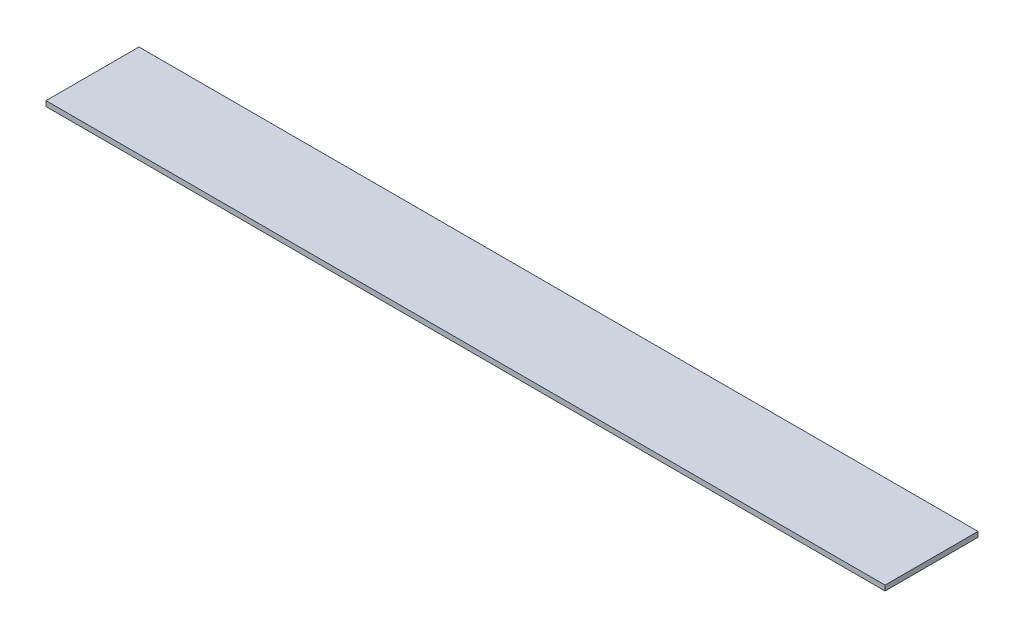
SolidWorks part; units mm, degrees
material "Liga 7079"
ref_plane "Plano frontal" through (0, 0, 0) normal (0, 0, 1) x (1, 0, 0)
ref_plane "Plano superior" through (0, 0, 0) normal (0, 1, 0) x (1, 0, 0)
ref_plane "Plano direito" through (0, 0, 0) normal (1, 0, 0) x (0, 0, -1)
sketch "Esboço1" plane through (0, 0, 0) normal (1, 0, 0) x (0, 0, -1)
  line L1 (-18, 0) -> (18, 0)
  dimension "D1" = 36
sheet metal parameters "Chapa metálica2" thickness 2 parameters "D1"=0.7366, "Espessura"=2
base flange "Flange-base2" sketch "Esboço1" end condition mid plane depth 325 reverse direction no thickness 2 reverse thickness direction no bend radius 0.7366
flat pattern "Padrão-Plano2" [suppressed]
sketch "Curva-Linhas2" plane through (0, 0, 0) normal (0, 1, 0) x (-1, 0, 0)
